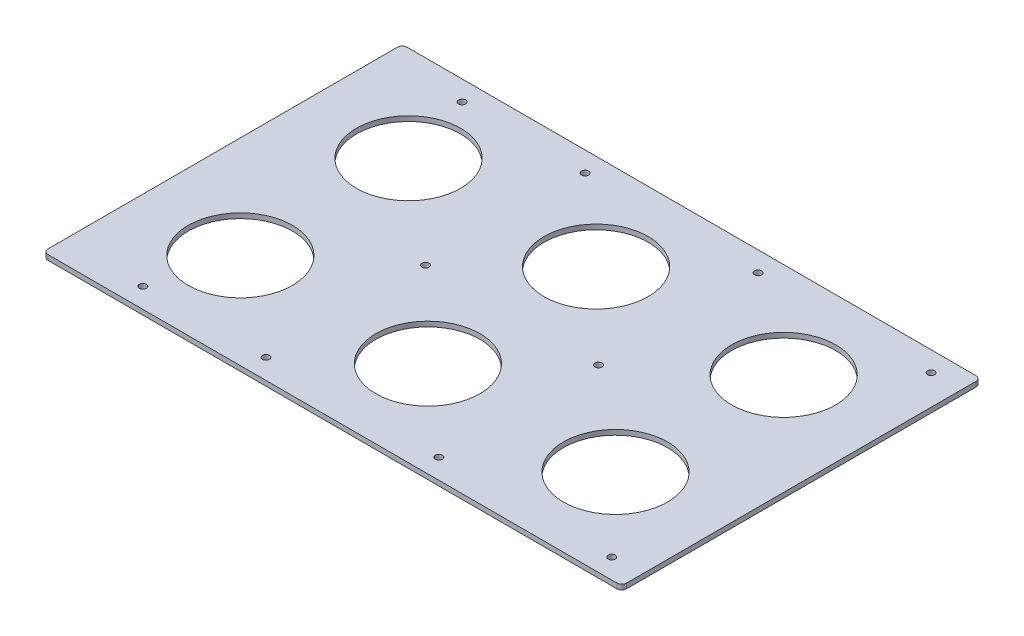
SolidWorks part; units mm, degrees
material "ABS"
ref_plane "Front" through (0, 0, 0) normal (0, 0, 1) x (1, 0, 0)
ref_plane "Top" through (0, 0, 0) normal (0, 1, 0) x (1, 0, 0)
ref_plane "Right" through (0, 0, 0) normal (1, 0, 0) x (0, 0, -1)
sketch "Sketch1" plane through (0, 0, 0) normal (0, 1, 0) x (1, 0, 0)
  line L1 (-180.975, 114.3) -> (180.975, 114.3)
  line L2 (-184.15, 111.125) -> (-184.15, -111.125)
  line L3 (-180.975, -114.3) -> (180.975, -114.3)
  line L4 (184.15, 111.125) -> (184.15, -111.125)
  line L5 (-184.15, 114.3) -> (184.15, -114.3) construction
  line L6 (-184.15, -114.3) -> (184.15, 114.3) construction
  circle A0 centre (119.38, -53.5178) radius 33.147
  arc A1 (-184.15, -111.125) -> (-180.975, -114.3) centre (-180.975, -111.125) ccw
  arc A2 (180.975, -114.3) -> (184.15, -111.125) centre (180.975, -111.125) ccw
  arc A3 (184.15, 111.125) -> (180.975, 114.3) centre (180.975, 111.125) ccw
  arc A4 (-180.975, 114.3) -> (-184.15, 111.125) centre (-180.975, 111.125) ccw
  circle A6 centre (-55.0333, -101.6) radius 2.2479 construction
  circle A7 centre (55.0333, -101.6) radius 2.2479 construction
  circle A8 centre (165.1, -101.6) radius 2.2479 construction
  circle A9 centre (165.1, 101.6) radius 2.2479 construction
  circle A10 centre (55.0333, 101.6) radius 2.2479 construction
  circle A11 centre (-55.0333, 101.6) radius 2.2479 construction
  circle A14 centre (-55.0333, -101.6) radius 2.2479
  circle A15 centre (55.0333, -101.6) radius 2.2479
  circle A16 centre (165.1, -101.6) radius 2.2479
  circle A17 centre (165.1, 101.6) radius 2.2479
  circle A18 centre (55.0333, 101.6) radius 2.2479
  circle A19 centre (-55.0333, 101.6) radius 2.2479
  circle A21 centre (-55.0333, 0) radius 2.2479 construction
  circle A22 centre (55.0333, 0) radius 2.2479 construction
  circle A23 centre (-55.0333, 0) radius 2.2479
  circle A24 centre (55.0333, 0) radius 2.2479
  circle A25 centre (119.38, 53.5178) radius 33.147
  circle A26 centre (0, 53.5178) radius 33.147
  circle A27 centre (0, -53.5178) radius 33.147
  circle A28 centre (-119.38, 53.5178) radius 33.147
  circle A29 centre (-119.38, -53.5178) radius 33.147
  circle A30 centre (-133.35, -101.6) radius 2.2479 construction
  circle A31 centre (-133.35, -101.6) radius 2.2479
  circle A32 centre (-133.35, 101.6) radius 2.2479 construction
  circle A33 centre (-133.35, 101.6) radius 2.2479
  point P0 (0, 0)
  dimension "D3" = 66.294
  dimension "D4" = 3.175
  dimension "D1" = 368.3
  dimension "D2" = 228.6
extrude "Boss-Extrude1" add sketch "Sketch1" along normal blind 3.175
